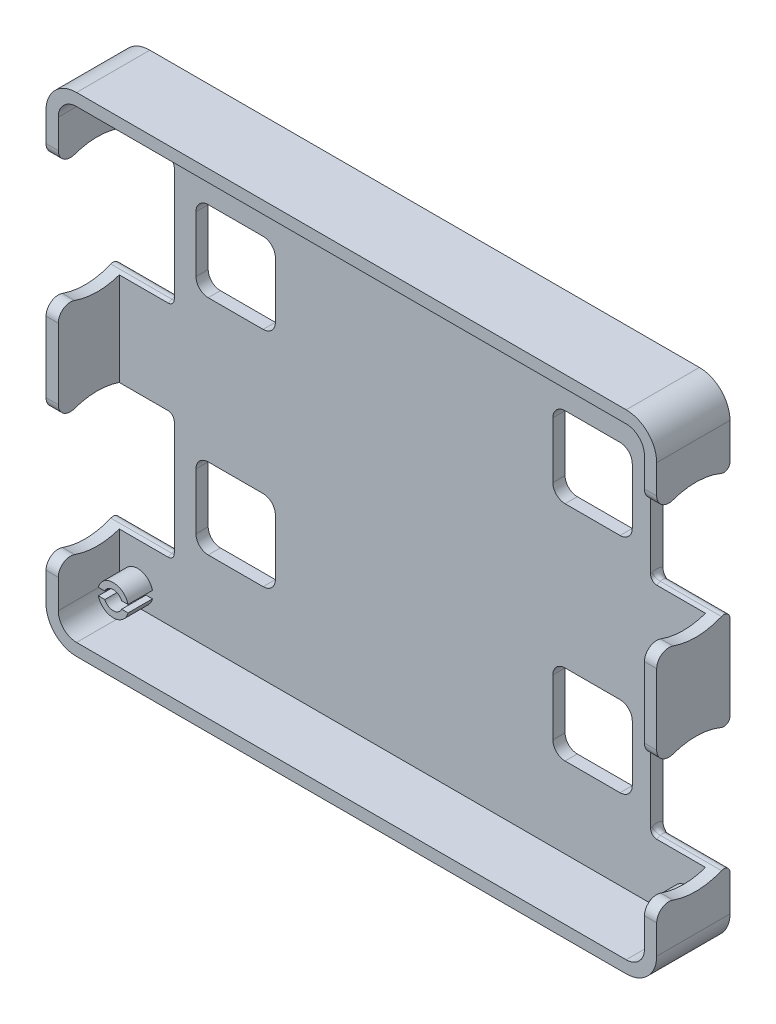
SolidWorks part; units mm, degrees
ref_plane "Plan de face" through (0, 0, 0) normal (0, 0, 1) x (1, 0, 0)
ref_plane "Plan de dessus" through (0, 0, 0) normal (0, 1, 0) x (1, 0, 0)
ref_plane "Plan de droite" through (0, 0, 0) normal (1, 0, 0) x (0, 0, -1)
sketch "Esquisse1" plane through (0, 0, 0) normal (0, 0, 1) x (1, 0, 0)
  line L0 (-226.3851, -200.1385) -> (223.6149, -200.1385)
  line L1 (248.6149, -175.1385) -> (248.6149, 174.8615)
  line L2 (223.6149, 199.8615) -> (-226.3851, 199.8615)
  line L3 (-251.3851, 174.8615) -> (-251.3851, -175.1385)
  line L4 (-241.3851, 174.8615) -> (-241.3851, -175.1385)
  line L5 (-226.3851, -190.1385) -> (223.6149, -190.1385)
  line L6 (238.6149, -175.1385) -> (238.6149, 174.8615)
  line L7 (223.6149, 189.8615) -> (-226.3851, 189.8615)
  arc A0 (223.6149, -200.1385) -> (248.6149, -175.1385) centre (223.6149, -175.1385) ccw
  arc A1 (248.6149, 174.8615) -> (223.6149, 199.8615) centre (223.6149, 174.8615) ccw
  arc A2 (-226.3851, 199.8615) -> (-251.3851, 174.8615) centre (-226.3851, 174.8615) ccw
  arc A3 (-251.3851, -175.1385) -> (-226.3851, -200.1385) centre (-226.3851, -175.1385) ccw
  arc A4 (-241.3851, -175.1385) -> (-226.3851, -190.1385) centre (-226.3851, -175.1385) ccw
  arc A5 (223.6149, -190.1385) -> (238.6149, -175.1385) centre (223.6149, -175.1385) ccw
  arc A6 (238.6149, 174.8615) -> (223.6149, 189.8615) centre (223.6149, 174.8615) ccw
  arc A7 (-226.3851, 189.8615) -> (-241.3851, 174.8615) centre (-226.3851, 174.8615) ccw
  dimension "D1" = 10
extrude "Boss.-Extru.1" add sketch "Esquisse1" along normal blind 50
sketch "Esquisse2" plane through (0, 0, 0) normal (0, 0, -1) x (-1, 0, 0)
  line L4 (251.3851, -175.1385) -> (251.3851, 174.8615)
  line L5 (226.3851, 199.8615) -> (-223.6149, 199.8615)
  line L6 (-248.6149, 174.8615) -> (-248.6149, -175.1385)
  line L7 (-223.6149, -200.1385) -> (226.3851, -200.1385)
  line L8 (251.3851, -175.1385) -> (251.3851, 174.8615)
  line L9 (226.3851, 199.8615) -> (-223.6149, 199.8615)
  line L10 (-248.6149, 174.8615) -> (-248.6149, -175.1385)
  line L11 (-223.6149, -200.1385) -> (226.3851, -200.1385)
  arc A4 (226.3851, -200.1385) -> (251.3851, -175.1385) centre (226.3851, -175.1385) ccw
  arc A5 (251.3851, 174.8615) -> (226.3851, 199.8615) centre (226.3851, 174.8615) ccw
  arc A6 (-223.6149, 199.8615) -> (-248.6149, 174.8615) centre (-223.6149, 174.8615) ccw
  arc A7 (-248.6149, -175.1385) -> (-223.6149, -200.1385) centre (-223.6149, -175.1385) ccw
  arc A8 (226.3851, -200.1385) -> (251.3851, -175.1385) centre (226.3851, -175.1385) ccw
  arc A9 (251.3851, 174.8615) -> (226.3851, 199.8615) centre (226.3851, 174.8615) ccw
  arc A10 (-223.6149, 199.8615) -> (-248.6149, 174.8615) centre (-223.6149, 174.8615) ccw
  arc A11 (-248.6149, -175.1385) -> (-223.6149, -200.1385) centre (-223.6149, -175.1385) ccw
  dimension "D1" = 0
extrude "Boss.-Extru.2" add sketch "Esquisse2" along normal blind 10
sketch "Esquisse3" plane through (0, 0, 0) normal (0, 0, 1) x (1, 0, 0)
  line L0 (-233.8851, 174.8615) -> (-218.8851, 174.8615) construction
  line L1 (-238.5197, 177.8615) -> (-233.2589, 177.8615)
  line L2 (-238.5197, 171.8615) -> (-233.2589, 171.8615)
  line L3 (-219.5112, 177.8615) -> (-214.2504, 177.8615)
  line L4 (-219.5112, 171.8615) -> (-214.2504, 171.8615)
  arc A0 (-226.3851, 189.8615) -> (-241.3851, 174.8615) centre (-226.3851, 174.8615) ccw construction
  arc A1 (-226.3851, 189.8615) -> (-241.3851, 174.8615) centre (-226.3851, 174.8615) ccw
  arc A2 (-241.3851, -175.1385) -> (-226.3851, -190.1385) centre (-226.3851, -175.1385) ccw construction
  arc A3 (-241.3851, -175.1385) -> (-226.3851, -190.1385) centre (-226.3851, -175.1385) ccw
  arc A4 (-238.5197, 171.8615) -> (-214.2504, 171.8615) centre (-226.3851, 174.8615) ccw
  arc A5 (-233.2589, 171.8615) -> (-219.5112, 171.8615) centre (-226.3851, 174.8615) ccw
  arc A6 (-221.723, 180.7364) -> (-230.8915, 168.8663) centre (0, 0) ccw
  arc A7 (-214.2504, 177.8615) -> (-238.5197, 177.8615) centre (-226.3851, 174.8615) ccw
  arc A8 (-219.5112, 177.8615) -> (-233.2589, 177.8615) centre (-226.3851, 174.8615) ccw
  dimension "D1" = 25
  dimension "D2" = 15
  dimension "D3" = 3
extrude "Boss.-Extru.3" add sketch "Esquisse3" along normal blind 20 contours A5 A6 A4 L4 | A8 A6 A7 L1 region at (-226.3851, 182.562, 0) region at (-226.3851, 167.161, 0)
ref_plane "Plan1" through (-1.3851, 0, 0) normal (1, 0, 0) x (0, 0, -1)
mirror "Symétrie1" about plane through (-1.3851, 0, 0) normal (1, 0, 0) of "Boss.-Extru.3"
ref_plane "Plan2" through (0, -0.1385, 0) normal (0, 1, 0) x (1, 0, 0)
mirror "Symétrie2" about plane through (0, -0.1385, 0) normal (0, 1, 0) of "Symétrie1", "Boss.-Extru.3"
sketch "Esquisse4" plane through (248.6149, 0, 0) normal (1, 0, 0) x (0, 0, -1)
  line L0 (-50, -0.1385) -> (10, -0.1385) construction
  line L1 (-50, -175.1385) -> (-50, 174.8615) construction
  line L2 (10, 174.8615) -> (10, -175.1385) construction
  circle A0 centre (-18.0867, -90.2354) radius 55
  circle A1 centre (-18.0867, 89.9584) radius 55
  dimension "D1" = 110
extrude "Enlèv. mat.-Extru.1" cut sketch "Esquisse4" against normal blind 55
mirror "Symétrie3" about plane through (-1.3851, 0, 0) normal (1, 0, 0) of "Enlèv. mat.-Extru.1"
fillet "Congé1" radius 10 8 edges at (243.6149, 134.7528, 50) (243.6149, 45.164, 50) (243.6149, -45.441, 50) (243.6149, -135.0298, 50) (-246.3851, 134.7528, 50) (-246.3851, 45.164, 50) (-246.3851, -45.441, 50) (-246.3851, -135.0298, 50)
fillet "Congé2" radius 5 8 edges at (221.1149, 137.2462, -10) (221.1149, 42.6706, -10) (221.1149, -42.9476, -10) (221.1149, -137.5232, -10) (-223.8851, -137.5232, -10) (-223.8851, -42.9476, -10) (-223.8851, 42.6706, -10) (-223.8851, 137.2462, -10)
fillet "Congé3" radius 5 16 edges at (193.6149, -141.4555, -7.7731) (193.6149, -141.6117, -1.5469) (-196.3851, -141.4555, -7.7731) (-196.3851, -39.0154, -7.7731) (-196.3851, 38.7384, -7.7731) (-196.3851, 141.1785, -7.7731) (193.6149, 141.1785, -7.7731) (193.6149, 38.7384, -7.7731) (193.6149, -39.0154, -7.7731) (-196.3851, -141.6117, -1.5469) (-196.3851, -38.8591, -1.5469) (-196.3851, 38.5821, -1.5469) (-196.3851, 141.3347, -1.5469) (193.6149, 141.3347, -1.5469) (193.6149, 38.5821, -1.5469) (193.6149, -38.8591, -1.5469)
sketch "Esquisse5" plane through (0, 0, -10) normal (0, 0, -1) x (-1, 0, 0)
  line L0 (0, -266.5677) -> (0, 267.5112) construction
  line L1 (178.6149, -58.2181) -> (113.607, -58.2181)
  line L2 (178.6149, -58.2181) -> (178.6149, -124.2089)
  line L3 (178.6149, -124.2089) -> (113.607, -124.2089)
  line L4 (113.607, -58.2181) -> (113.607, -124.2089)
  line L5 (332.5743, 0) -> (-340.8135, 0) construction
  line L6 (-178.6149, -124.2089) -> (-113.607, -124.2089)
  line L7 (-113.607, -58.2181) -> (-113.607, -124.2089)
  line L8 (-178.6149, -58.2181) -> (-113.607, -58.2181)
  line L9 (-178.6149, -58.2181) -> (-178.6149, -124.2089)
  line L10 (-178.6149, 58.2181) -> (-178.6149, 124.2089)
  line L11 (-178.6149, 58.2181) -> (-113.607, 58.2181)
  line L12 (-113.607, 58.2181) -> (-113.607, 124.2089)
  line L13 (-178.6149, 124.2089) -> (-113.607, 124.2089)
  line L14 (178.6149, 124.2089) -> (113.607, 124.2089)
  line L15 (113.607, 58.2181) -> (113.607, 124.2089)
  line L16 (178.6149, 58.2181) -> (113.607, 58.2181)
  line L17 (178.6149, 58.2181) -> (178.6149, 124.2089)
  line L18 (-193.6149, 43.2381) -> (-193.6149, 136.6787) construction
  dimension "D1" = 15
extrude "Enlèv. mat.-Extru.2" cut sketch "Esquisse5" against normal blind 10
fillet "Congé4" radius 10 16 edges at (-178.6149, 124.2089, -5) (-178.6149, 58.2181, -5) (-113.607, 124.2089, -5) (-113.607, 58.2181, -5) (-178.6149, -58.2181, -5) (-178.6149, -124.2089, -5) (-113.607, -58.2181, -5) (-113.607, -124.2089, -5) (113.607, 124.2089, -5) (178.6149, 124.2089, -5) (113.607, 58.2181, -5) (178.6149, 58.2181, -5) (113.607, -58.2181, -5) (178.6149, -58.2181, -5) (178.6149, -124.2089, -5) (113.607, -124.2089, -5)
